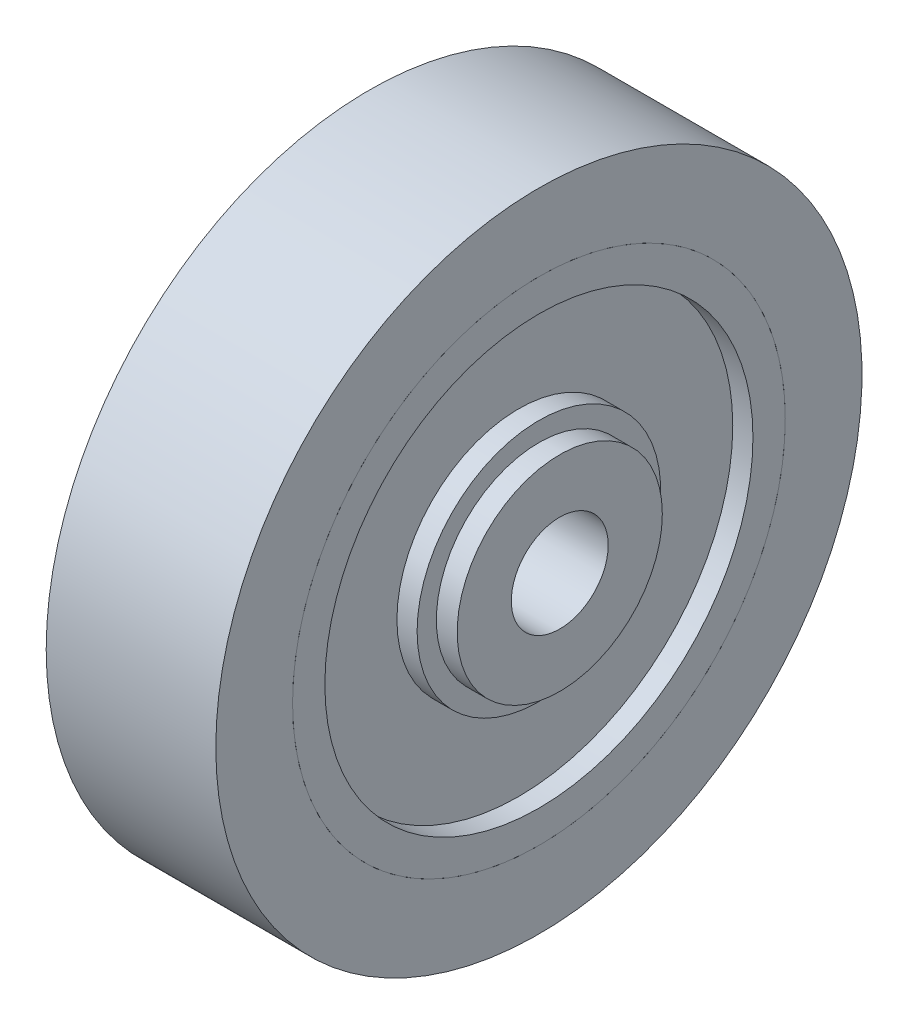
SolidWorks part; units mm, degrees
other "Clip"
other "Hub"
other "Rim"
other "Tire"
ref_plane "Front Plane" through (0, 0, 0) normal (0, 0, 1) x (1, 0, 0)
ref_plane "Top Plane" through (0, 0, 0) normal (0, 1, 0) x (1, 0, 0)
ref_plane "Right Plane" through (0, 0, 0) normal (1, 0, 0) x (0, 0, -1)
sketch "Sketch1" plane through (0, 0, 0) normal (1, 0, 0) x (0, 0, -1)
  line L0 (0, 15.25) -> (0, 20) construction
  circle A0 centre (0, 0) radius 20
  circle A1 centre (0, 0) radius 15.25
  circle A2 centre (0, 0) radius 20 construction
  dimension "D2" = 4.75
extrude "Boss-Extrude1" add sketch "Sketch1" along normal blind 10.5
ref_plane "Plane4" through (0, 0, 0) normal (-1, 0, 0) x (0, 0, 1)
sketch "Sketch2" plane through (10.5, 0, 0) normal (1, 0, 0) x (0, 0, -1)
  circle A0 centre (0, 0) radius 15.25 construction
  circle A1 centre (0, 0) radius 15.25
  circle A2 centre (0, 0) radius 13.25
  dimension "D1" = 2
extrude "Boss-Extrude2" add sketch "Sketch2" against normal up to surface (10.5 mm away) separate body up to face at (0, 0, -20)
ref_plane "Mid-Plane" through (5.25, 0, 0) normal (1, 0, 0) x (0, 0, -1)
ref_axis "Axis1" through (0, 0, 0) along (1, 0, 0)
sketch "Sketch3" plane through (5.25, 0, 0) normal (1, 0, 0) x (0, 0, -1)
  line L1 (7.3323, 0) -> (3.6662, 6.35)
  line L2 (3.6662, 6.35) -> (-3.6662, 6.35)
  line L3 (-3.6662, 6.35) -> (-7.3323, 0)
  line L4 (-7.3323, 0) -> (-3.6662, -6.35)
  line L5 (-3.6662, -6.35) -> (3.6662, -6.35)
  line L6 (3.6662, -6.35) -> (7.3323, 0)
  circle A0 centre (0, 0) radius 6.35 construction
  circle A1 centre (0, 0) radius 13.25 construction
  circle A2 centre (0, 0) radius 13.25
  dimension "D1" = 12.7
extrude "Boss-Extrude3" add sketch "Sketch3" along normal offset from surface 1.25 and the other way offset from surface 1.25 up to face at (10.5, 0, -13.25) other way up to face at (0, 0, -15.25)
sketch "Sketch4" plane through (1.25, 0, 0) normal (-1, 0, 0) x (0, 0, 1)
  circle A0 centre (0, 0) radius 7.625
  circle A1 centre (0, 0) radius 3
  dimension "D1" = 15.25
  dimension "D2" = 6
extrude "Boss-Extrude4" add sketch "Sketch4" along normal up to surface (1.25 mm away) separate body up to face at (0, 0, -15.25)
sketch "Sketch5" plane through (1.25, 0, 0) normal (1, 0, 0) x (0, 0, -1)
  line L0 (-7.3323, 0) -> (-3.6662, 6.35) construction
  line L1 (-3.6662, 6.35) -> (3.6662, 6.35) construction
  line L2 (3.6662, 6.35) -> (7.3323, 0) construction
  line L3 (7.3323, 0) -> (3.6662, -6.35) construction
  line L4 (3.6662, -6.35) -> (-3.6662, -6.35) construction
  line L5 (-3.6662, -6.35) -> (-7.3323, 0) construction
  line L6 (-7.3323, 0) -> (-3.6662, 6.35)
  line L7 (-3.6662, 6.35) -> (3.6662, 6.35)
  line L8 (3.6662, 6.35) -> (7.3323, 0)
  line L9 (7.3323, 0) -> (3.6662, -6.35)
  line L10 (3.6662, -6.35) -> (-3.6662, -6.35)
  line L11 (-3.6662, -6.35) -> (-7.3323, 0)
  circle A0 centre (0, 0) radius 3 construction
  circle A1 centre (0, 0) radius 3
extrude "Boss-Extrude5" add sketch "Sketch5" along normal up to surface (8 mm away) up to face at (9.25, 0, 0)
sketch "Sketch6" plane through (9.25, 0, 0) normal (1, 0, 0) x (0, 0, -1)
  circle A0 centre (0, 0) radius 3 construction
  circle A1 centre (0, 0) radius 3
  circle A2 centre (0, 0) radius 5.94
  dimension "D1" = 11.88
extrude "Boss-Extrude6" add sketch "Sketch6" along normal up to surface (1.25 mm away) up to face at (10.5, 0, -13.25)
sketch "Sketch7" plane through (10.5, 0, 0) normal (1, 0, 0) x (0, 0, -1)
  line L0 (3.6662, -6.35) -> (7.3323, 0) construction
  circle A0 centre (0, 0) radius 6.35
  circle A1 centre (0, 0) radius 3 construction
  circle A2 centre (0, 0) radius 3
extrude "Boss-Extrude7" add sketch "Sketch7" along normal blind 1.29
ref_plane "Plane2" through (0, 0, 0) normal (0, 1, 0) x (1, 0, 0)
sketch "Sketch8" plane through (0, 6.35, 0) normal (0, 1, 0) x (1, 0, 0)
  line L0 (1.25, 0) -> (9.25, 0) construction
  line L1 (1.25, 3.6662) -> (1.25, -3.6662) construction
  line L2 (9.25, 3.6662) -> (9.25, -3.6662) construction
  circle A0 centre (5.25, 0) radius 1.5
  dimension "D1" = 3
extrude "Cut-Extrude1" cut sketch "Sketch8" against normal up to surface (6.35 mm away) up to plane "Plane2"
sketch "Sketch9" plane through (9.25, 0, 0) normal (1, 0, 0) x (0, 0, -1)
  circle A0 centre (0, 0) radius 5.94 construction
  circle A1 centre (0, 0) radius 5.94
  circle A2 centre (0, 0) radius 7.54
  dimension "D1" = 1.6
extrude "Boss-Extrude8" add sketch "Sketch9" along normal up to surface (1.25 mm away) separate body up to face at (10.5, 0, -5.94)
ref_plane "Plane3" through (0, 0, 0) normal (0, 0, 1) x (1, 0, 0)
